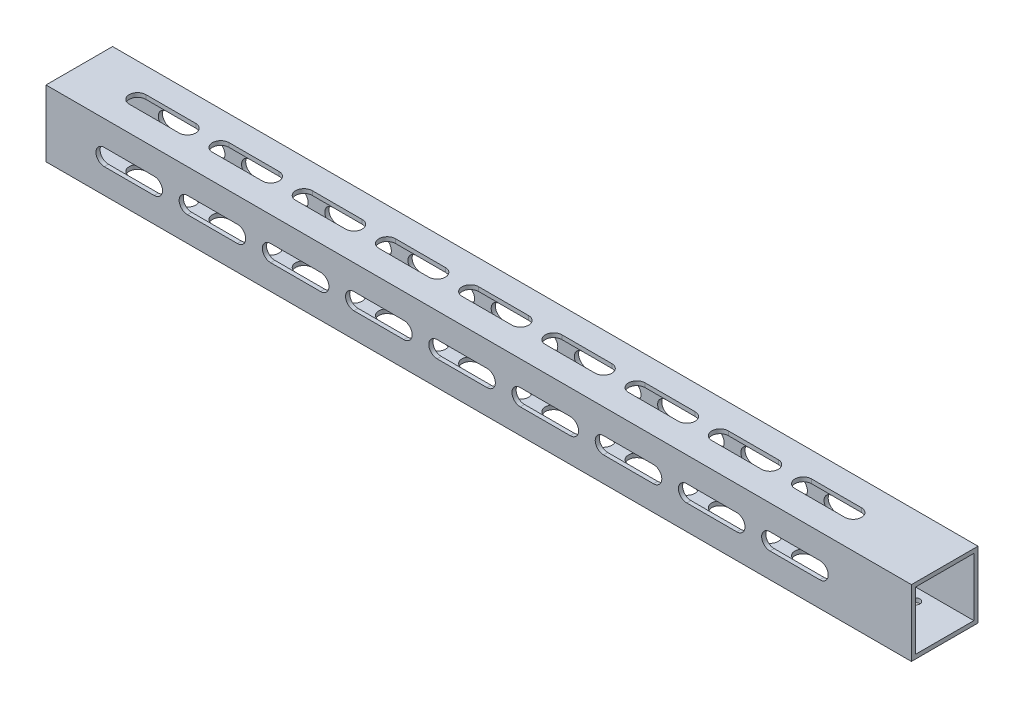
SolidWorks part; units mm, degrees
material "6061-T6 (SS)"
ref_plane "Front" through (0, 0, 0) normal (0, 0, 1) x (1, 0, 0)
ref_plane "Top" through (0, 0, 0) normal (0, 1, 0) x (1, 0, 0)
ref_plane "Right" through (0, 0, 0) normal (1, 0, 0) x (0, 0, -1)
sketch "Sketch1" plane through (0, 0, 0) normal (1, 0, 0) x (0, 0, -1)
  line L1 (-12.7, -12.7) -> (12.7, -12.7)
  line L2 (-12.7, -12.7) -> (-12.7, 12.7)
  line L3 (-12.7, 12.7) -> (12.7, 12.7)
  line L4 (12.7, -12.7) -> (12.7, 12.7)
  line L5 (-12.7, -12.7) -> (12.7, 12.7) construction
  line L6 (-12.7, 12.7) -> (12.7, -12.7) construction
  point P0 (0, 0)
  dimension "D1" = 25.4
extrude "Extrude-Thin1" add sketch "Sketch1" along normal up to surface (330.2 mm away) thin thin type one direction reverse wall 1.5875
sketch "Sketch4" plane through (0, -12.7, 0) normal (0, -1, 0) x (1, 0, 0)
  line L0 (0, 12.7) -> (0, -12.7) construction
  line L2 (17.4625, -6.35) -> (0, 0) construction
  line L3 (0, 0) -> (17.4625, 6.35) construction
  line L4 (165.1, -12.7) -> (165.1, 38.5816) construction
  line L5 (330.2, -12.7) -> (0, -12.7) construction
  point P0 (17.4625, -6.35)
  point P2 (26.9875, 6.35)
  point P7 (26.9875, -6.35)
  point P10 (17.4625, 6.35)
  point P22 (71.4375, -6.35)
  point P24 (61.9125, -6.35)
  point P26 (61.9125, 6.35)
  point P28 (71.4375, 6.35)
  point P37 (258.7625, 6.35)
  point P38 (268.2875, 6.35)
  point P39 (268.2875, -6.35)
  point P40 (258.7625, -6.35)
  point P41 (312.7375, 6.35)
  point P42 (303.2125, -6.35)
  point P43 (303.2125, 6.35)
  point P44 (312.7375, -6.35)
  dimension "D1" = 17.4625
  dimension "D2" = 9.525
  dimension "D3" = 12.7
  dimension "D4" = 44.45
  dimension "D5" = 9.525
hole_wizard "#30 (0.13) Diameter Hole1" positions "Sketch4" profile "Sketch3" hole size "#30" standard "ANSI Inch" end condition up to next
sketch "Sketch3" plane through (17.4625, -12.7, -6.35) normal (1, 0, 0) x (0, 0, -1)
  line L0 (0, 0) -> (0, 1.5875)
  line L1 (0, 1.5875) -> (1.651, 1.5875)
  line L2 (1.651, 1.5875) -> (1.651, 0)
  line L5 (1.651, 0) -> (0, 0)
  line L11 (0, -6.35) -> (0, 107.95) construction
  dimension "Thru Hole Dia." = 3.302
  dimension "Thru Hole Depth" = 1.5875
sketch "Sketch5" plane through (0, 12.7, 0) normal (0, 1, 0) x (1, 0, 0)
  line L0 (22.225, 0) -> (41.275, 0) construction
  line L1 (22.225, 3.175) -> (41.275, 3.175)
  line L2 (22.225, -3.175) -> (41.275, -3.175)
  line L3 (0, 12.7) -> (0, -12.7) construction
  line L4 (53.975, 0) -> (73.025, 0) construction
  line L5 (53.975, 3.175) -> (73.025, 3.175)
  line L6 (53.975, -3.175) -> (73.025, -3.175)
  line L7 (85.725, 0) -> (104.775, 0) construction
  line L8 (85.725, 3.175) -> (104.775, 3.175)
  line L9 (85.725, -3.175) -> (104.775, -3.175)
  line L10 (117.475, 0) -> (136.525, 0) construction
  line L11 (117.475, 3.175) -> (136.525, 3.175)
  line L12 (117.475, -3.175) -> (136.525, -3.175)
  line L13 (149.225, 0) -> (168.275, 0) construction
  line L14 (149.225, 3.175) -> (168.275, 3.175)
  line L15 (149.225, -3.175) -> (168.275, -3.175)
  line L16 (180.975, 0) -> (200.025, 0) construction
  line L17 (180.975, 3.175) -> (200.025, 3.175)
  line L18 (180.975, -3.175) -> (200.025, -3.175)
  line L19 (212.725, 0) -> (231.775, 0) construction
  line L20 (212.725, 3.175) -> (231.775, 3.175)
  line L21 (212.725, -3.175) -> (231.775, -3.175)
  line L22 (244.475, 0) -> (263.525, 0) construction
  line L23 (244.475, 3.175) -> (263.525, 3.175)
  line L24 (244.475, -3.175) -> (263.525, -3.175)
  line L25 (276.225, 0) -> (295.275, 0) construction
  line L26 (276.225, 3.175) -> (295.275, 3.175)
  line L27 (276.225, -3.175) -> (295.275, -3.175)
  arc A0 (22.225, 3.175) -> (22.225, -3.175) centre (22.225, 0) ccw
  arc A1 (41.275, -3.175) -> (41.275, 3.175) centre (41.275, 0) ccw
  arc A2 (53.975, 3.175) -> (53.975, -3.175) centre (53.975, 0) ccw
  arc A3 (73.025, -3.175) -> (73.025, 3.175) centre (73.025, 0) ccw
  arc A4 (85.725, 3.175) -> (85.725, -3.175) centre (85.725, 0) ccw
  arc A5 (104.775, -3.175) -> (104.775, 3.175) centre (104.775, 0) ccw
  arc A6 (117.475, 3.175) -> (117.475, -3.175) centre (117.475, 0) ccw
  arc A7 (136.525, -3.175) -> (136.525, 3.175) centre (136.525, 0) ccw
  arc A8 (149.225, 3.175) -> (149.225, -3.175) centre (149.225, 0) ccw
  arc A9 (168.275, -3.175) -> (168.275, 3.175) centre (168.275, 0) ccw
  arc A10 (180.975, 3.175) -> (180.975, -3.175) centre (180.975, 0) ccw
  arc A11 (200.025, -3.175) -> (200.025, 3.175) centre (200.025, 0) ccw
  arc A12 (212.725, 3.175) -> (212.725, -3.175) centre (212.725, 0) ccw
  arc A13 (231.775, -3.175) -> (231.775, 3.175) centre (231.775, 0) ccw
  arc A14 (244.475, 3.175) -> (244.475, -3.175) centre (244.475, 0) ccw
  arc A15 (263.525, -3.175) -> (263.525, 3.175) centre (263.525, 0) ccw
  arc A16 (276.225, 3.175) -> (276.225, -3.175) centre (276.225, 0) ccw
  arc A17 (295.275, -3.175) -> (295.275, 3.175) centre (295.275, 0) ccw
  point P2 (31.75, 0)
  point P13 (63.5, 0)
  point P20 (95.25, 0)
  point P27 (127, 0)
  point P34 (158.75, 0)
  point P41 (190.5, 0)
  point P48 (222.25, 0)
  point P55 (254, 0)
  point P62 (285.75, 0)
  dimension "D3" = 22.225
  dimension "D5" = 12.7
  dimension "D1" = 6.35
  dimension "D2" = 19.05
  dimension "D4" = 9
extrude "Cut-Extrude1" cut sketch "Sketch5" against normal through all
sketch "Sketch6" plane through (0, 0, 12.7) normal (0, 0, 1) x (1, 0, 0)
  line L0 (22.225, 0) -> (41.275, 0) construction
  line L1 (22.225, 3.175) -> (41.275, 3.175)
  line L2 (22.225, -3.175) -> (41.275, -3.175)
  line L3 (0, 12.7) -> (0, -12.7) construction
  line L4 (53.975, 0) -> (73.025, 0) construction
  line L5 (53.975, 3.175) -> (73.025, 3.175)
  line L6 (53.975, -3.175) -> (73.025, -3.175)
  line L7 (85.725, 0) -> (104.775, 0) construction
  line L8 (85.725, 3.175) -> (104.775, 3.175)
  line L9 (85.725, -3.175) -> (104.775, -3.175)
  line L10 (117.475, 0) -> (136.525, 0) construction
  line L11 (117.475, 3.175) -> (136.525, 3.175)
  line L12 (117.475, -3.175) -> (136.525, -3.175)
  line L13 (149.225, 0) -> (168.275, 0) construction
  line L14 (149.225, 3.175) -> (168.275, 3.175)
  line L15 (149.225, -3.175) -> (168.275, -3.175)
  line L16 (180.975, 0) -> (200.025, 0) construction
  line L17 (180.975, 3.175) -> (200.025, 3.175)
  line L18 (180.975, -3.175) -> (200.025, -3.175)
  line L19 (212.725, 0) -> (231.775, 0) construction
  line L20 (212.725, 3.175) -> (231.775, 3.175)
  line L21 (212.725, -3.175) -> (231.775, -3.175)
  line L22 (244.475, 0) -> (263.525, 0) construction
  line L23 (244.475, 3.175) -> (263.525, 3.175)
  line L24 (244.475, -3.175) -> (263.525, -3.175)
  line L25 (276.225, 0) -> (295.275, 0) construction
  line L26 (276.225, 3.175) -> (295.275, 3.175)
  line L27 (276.225, -3.175) -> (295.275, -3.175)
  arc A0 (22.225, 3.175) -> (22.225, -3.175) centre (22.225, 0) ccw
  arc A1 (41.275, -3.175) -> (41.275, 3.175) centre (41.275, 0) ccw
  arc A2 (53.975, 3.175) -> (53.975, -3.175) centre (53.975, 0) ccw
  arc A3 (73.025, -3.175) -> (73.025, 3.175) centre (73.025, 0) ccw
  arc A4 (85.725, 3.175) -> (85.725, -3.175) centre (85.725, 0) ccw
  arc A5 (104.775, -3.175) -> (104.775, 3.175) centre (104.775, 0) ccw
  arc A6 (117.475, 3.175) -> (117.475, -3.175) centre (117.475, 0) ccw
  arc A7 (136.525, -3.175) -> (136.525, 3.175) centre (136.525, 0) ccw
  arc A8 (149.225, 3.175) -> (149.225, -3.175) centre (149.225, 0) ccw
  arc A9 (168.275, -3.175) -> (168.275, 3.175) centre (168.275, 0) ccw
  arc A10 (180.975, 3.175) -> (180.975, -3.175) centre (180.975, 0) ccw
  arc A11 (200.025, -3.175) -> (200.025, 3.175) centre (200.025, 0) ccw
  arc A12 (212.725, 3.175) -> (212.725, -3.175) centre (212.725, 0) ccw
  arc A13 (231.775, -3.175) -> (231.775, 3.175) centre (231.775, 0) ccw
  arc A14 (244.475, 3.175) -> (244.475, -3.175) centre (244.475, 0) ccw
  arc A15 (263.525, -3.175) -> (263.525, 3.175) centre (263.525, 0) ccw
  arc A16 (276.225, 3.175) -> (276.225, -3.175) centre (276.225, 0) ccw
  arc A17 (295.275, -3.175) -> (295.275, 3.175) centre (295.275, 0) ccw
  point P3 (31.75, 0)
  point P13 (63.5, 0)
  point P20 (95.25, 0)
  point P27 (127, 0)
  point P34 (158.75, 0)
  point P41 (190.5, 0)
  point P48 (222.25, 0)
  point P55 (254, 0)
  point P62 (285.75, 0)
  dimension "D3" = 22.225
  dimension "D5" = 12.7
  dimension "D1" = 6.35
  dimension "D2" = 19.05
  dimension "D4" = 9
extrude "Cut-Extrude2" cut sketch "Sketch6" against normal through all
